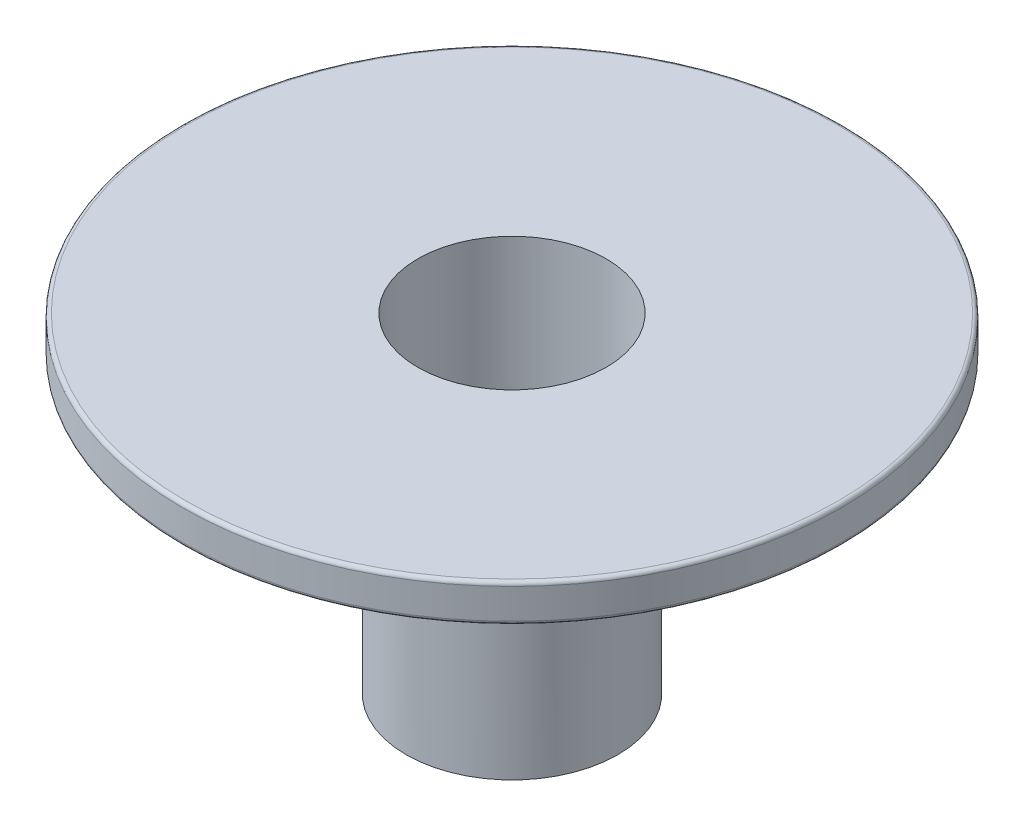
SolidWorks part; units mm, degrees
ref_plane "Спереди" through (0, 0, 0) normal (0, 0, 1) x (1, 0, 0)
ref_plane "Сверху" through (0, 0, 0) normal (0, 1, 0) x (1, 0, 0)
ref_plane "Справа" through (0, 0, 0) normal (1, 0, 0) x (0, 0, -1)
sketch "Эскиз1" plane through (0, 0, 0) normal (0, 1, 0) x (1, 0, 0)
  circle A0 centre (0, 0) radius 22.5
  circle A1 centre (0, 0) radius 20
  dimension "D1" = 45
  dimension "D2" = 40
extrude "Бобышка-Вытянуть1" add sketch "Эскиз1" along normal blind 70
sketch "Эскиз3" plane through (0, 0, 0) normal (0, 0, 1) x (1, 0, 0)
  line L0 (0, 0) -> (0, 70) construction
  line L1 (22.5, 40) -> (27.5, 40)
  line L2 (0, 40) -> (22.5, 40) construction
  line L3 (45, 67) -> (65, 67)
  line L12 (27.5, 40) -> (27.5, 58)
  line L13 (27.5, 58) -> (45, 58)
  line L14 (45, 58) -> (45, 67)
  line L16 (22.5, 70) -> (22.5, 40)
  line L19 (70, 70) -> (22.5, 70)
  line L24 (65, 67) -> (65, 62)
  line L25 (65, 62) -> (70, 62)
  line L26 (70, 62) -> (70, 70)
  dimension "D1" = 70
  dimension "D2" = 40
  dimension "D3" = 22.5
  dimension "D4" = 5
  dimension "D5" = 18
  dimension "D6" = 9
  dimension "D7" = 22.5
  dimension "D8" = 47.5
  dimension "D9" = 5
  dimension "D10" = 5
revolve "Повернуть3" add sketch "Эскиз3" angle 360 about L0
fillet "Скругление1" radius 0.8 4 edges at (0, 70, -70) (0, 62, -70) (0, 62, -65) (0, 67, -65)
fillet "Скругление2" radius 0.8 5 edges at (0, 40, -22.5) (0, 40, -27.5) (0, 58, -27.5) (0, 58, -45) (0, 67, -45)
sketch "Эскиз5" plane through (0, 0, 0) normal (0, -1, 0) x (1, 0, 0)
  circle A0 centre (0, 0) radius 20
  circle A1 centre (0, 0) radius 11
  dimension "D1" = 40
  dimension "D2" = 22
extrude "Бобышка-Вытянуть3" add sketch "Эскиз5" against normal blind 11.7
sketch "Эскиз6" plane through (0, 11.7, 0) normal (0, 1, 0) x (1, 0, 0)
  line L0 (0, 0) -> (0, 11) construction
  circle A0 centre (0, 0) radius 11 construction
  circle A1 centre (0, 15.5) radius 3.2
  circle A2 centre (0, 0) radius 15.5 construction
  circle A3 centre (13.4234, -7.75) radius 3.2
  circle A4 centre (-13.4234, -7.75) radius 3.2
  point P15 (0, 0)
  dimension "D1" = 31
  dimension "6,4" = 6.4
  dimension "D2" = 3
extrude "Вырез-Вытянуть1" cut sketch "Эскиз6" against normal blind 7.5
